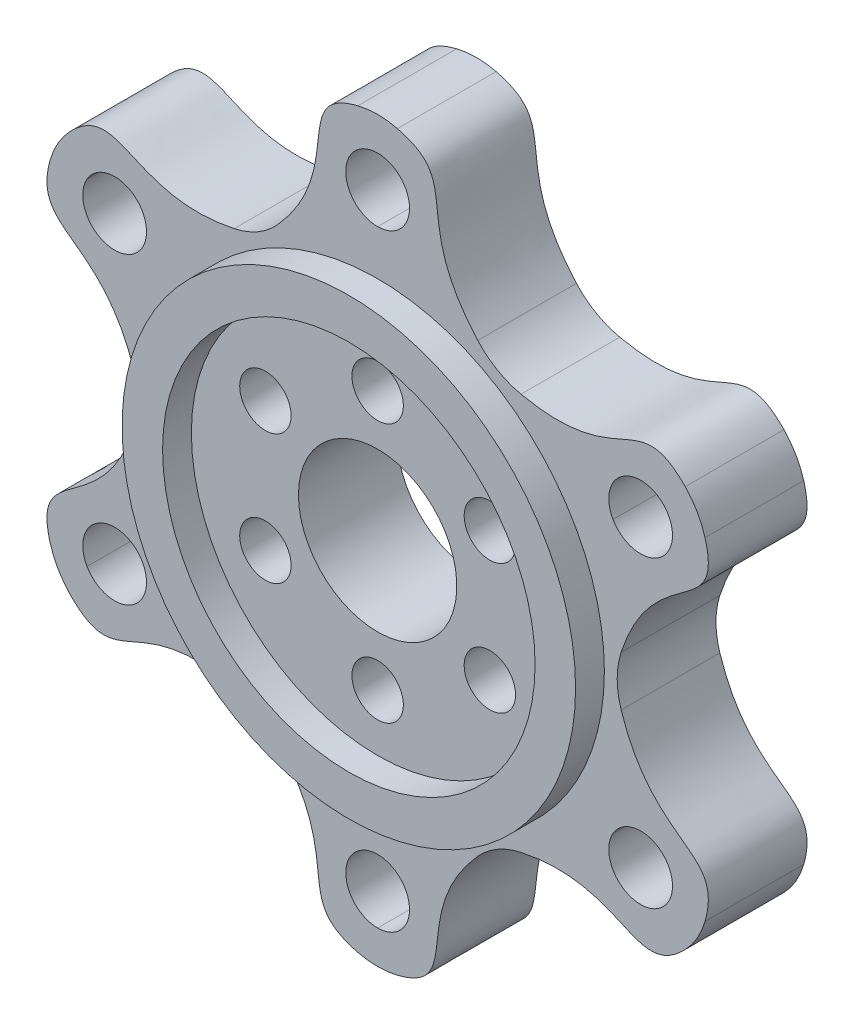
SolidWorks part; units mm, degrees
ref_plane "Front Plane" through (0, 0, 0) normal (0, 0, 1) x (1, 0, 0)
ref_plane "Top Plane" through (0, 0, 0) normal (0, 1, 0) x (1, 0, 0)
ref_plane "Right Plane" through (0, 0, 0) normal (1, 0, 0) x (0, 0, -1)
sketch "Sketch1" plane through (0, 0, 0) normal (0, 0, 1) x (1, 0, 0)
  line L0 (0, -55) -> (0, 55) construction
  line L1 (0, 0) -> (0, 45.72) construction
  circle A0 centre (0, 0) radius 9.779
  circle A1 centre (0, 0) radius 45.72
  circle A2 centre (0, 16.002) radius 3.175
  circle A3 centre (13.8581, 8.001) radius 3.175
  circle A4 centre (13.8581, -8.001) radius 3.175
  circle A5 centre (0, -16.002) radius 3.175
  circle A6 centre (-13.8581, -8.001) radius 3.175
  circle A7 centre (-13.8581, 8.001) radius 3.175
  circle A8 centre (0, 37.5) radius 3.937
  circle A10 centre (32.476, 18.75) radius 3.937
  circle A11 centre (32.476, -18.75) radius 3.937
  circle A12 centre (0, -37.5) radius 3.937
  circle A13 centre (-32.476, -18.75) radius 3.937
  circle A14 centre (-32.476, 18.75) radius 3.937
  point P21 (0, 0)
  point P36 (0, 0)
  dimension "D1" = 19.558
  dimension "D2" = 91.44
  dimension "D3" = 6.35
  dimension "D6" = 7.874
  dimension "D4" = 16.002
  dimension "D8" = 37.5
  dimension "D5" = 6
  dimension "D7" = 6
extrude "Boss-Extrude3" add sketch "Sketch1" along normal blind 12.192
sketch "Sketch2" plane through (0, 0, 12.192) normal (0, 0, 1) x (1, 0, 0)
  line L0 (0, -55) -> (0, 55) construction
  line L1 (-32.476, 18.75) -> (0, 37.5) construction
  line L2 (-16.238, 28.125) -> (-4.8895, 8.4689) construction
  line L3 (16.1981, 28.148) -> (4.8496, 8.4918) construction
  line L6 (32.476, -18.75) -> (32.476, 18.75) construction
  line L7 (32.476, 18.75) -> (0, 37.5) construction
  line L8 (55, 0) -> (-55, 0) construction
  circle A0 centre (0, 0) radius 27.94 construction
  circle A1 centre (0, 0) radius 45.72 construction
  circle A2 centre (0, 0) radius 9.779 construction
  circle A3 centre (0, 0) radius 45.72
  spline S0 degree 3 poles (-14.625, 25.3312) (-1.5745, 37.1177) (-13.1193, 43.9586) (0, 45.72) knots 0 0 0 0 1 1 1 1
  spline S1 degree 3 poles (14.625, 25.3312) (1.5745, 37.1177) (13.1193, 43.9586) (0, 45.72) knots 0 0 0 0 1 1 1 1
  spline S2 degree 3 poles (-29.25, 0) (-32.9321, 17.1953) (-44.6289, 10.6177) (-39.5947, 22.86) knots 0 0 0 0 1 1 1 1
  spline S3 degree 3 poles (-14.625, 25.3312) (-31.3576, 19.9224) (-31.5096, 33.3409) (-39.5947, 22.86) knots 0 0 0 0 1 1 1 1
  spline S4 degree 3 poles (-14.625, -25.3312) (-31.3576, -19.9224) (-31.5096, -33.3409) (-39.5947, -22.86) knots 0 0 0 0 1 1 1 1
  spline S5 degree 3 poles (-29.25, 0) (-32.9321, -17.1953) (-44.6289, -10.6177) (-39.5947, -22.86) knots 0 0 0 0 1 1 1 1
  spline S6 degree 3 poles (14.625, -25.3312) (31.3576, -19.9224) (31.5096, -33.3409) (39.5947, -22.86) knots 0 0 0 0 1 1 1 1
  spline S7 degree 3 poles (29.25, 0) (32.9321, -17.1953) (44.6289, -10.6177) (39.5947, -22.86) knots 0 0 0 0 1 1 1 1
  spline S8 degree 3 poles (14.625, -25.3312) (1.5745, -37.1177) (13.1193, -43.9586) (0, -45.72) knots 0 0 0 0 1 1 1 1
  spline S9 degree 3 poles (-14.625, -25.3312) (-1.5745, -37.1177) (-13.1193, -43.9586) (0, -45.72) knots 0 0 0 0 1 1 1 1
  spline S10 degree 3 poles (29.25, 0) (32.9321, 17.1953) (44.6289, 10.6177) (39.5947, 22.86) knots 0 0 0 0 1 1 1 1
  spline S11 degree 3 poles (14.625, 25.3312) (31.3576, 19.9224) (31.5096, 33.3409) (39.5947, 22.86) knots 0 0 0 0 1 1 1 1
  point P5 (-16.238, 28.125)
  point P6 (16.1981, 28.148)
  circle M8 centre (0, 0) radius 45.72
  dimension "D1" = 55.88
  dimension "D2" = 18.796
  dimension "D3" = 29.25
extrude "Cut-Extrude1" cut sketch "Sketch2" against normal blind 22.86 contours S1 S11 M8 | S5 S2 A3 | S10 S7 A3 | S6 S8 A3 | S9 S4 M8 | S3 S0 M8 region at (38.672, 0, 12.192) region at (19.336, 33.4909, 12.192) region at (19.336, -33.4909, 12.192) region at (-19.336, 33.4909, 12.192) region at (-19.336, -33.4909, 12.192) region at (-38.672, 0, 12.192)
sketch "Sketch4" plane through (0, 0, 12.192) normal (0, 0, 1) x (1, 0, 0)
  circle A0 centre (0, 0) radius 9.779 construction
  circle A1 centre (0, 0) radius 9.779 construction
  circle A2 centre (0, 0) radius 28
  circle A3 centre (0, 0) radius 23
  dimension "D1" = 56
  dimension "D2" = 46
extrude "Boss-Extrude4" add sketch "Sketch4" along normal blind 3.556 contours A2 | A3
ref_plane "Plane1" through (0, 0, 0) normal (1, 0, 0) x (0, 0, -1)
ref_plane "Plane2" through (0, 0, 0) normal (-0.5, -0.866, 0) x (-0.866, 0.5, 0)
ref_plane "Plane3" through (0, 0, 0) normal (-0.5, 0.866, 0) x (0.866, 0.5, 0)
split line "Split Line1"
split line "Split Line2"
split line "Split Line3"
ref_axis "Axis1" through (0, 0, 12.192) along (0, 0, -1)
fillet "Fillet1" radius 10 12 edges at (29.25, 0, 6.096) (39.5947, -22.86, 6.096) (0, -45.72, 6.096) (14.625, -25.3312, 6.096) (-14.625, -25.3312, 6.096) (-39.5947, -22.86, 6.096) (-29.25, 0, 6.096) (-39.5947, 22.86, 6.096) (-14.625, 25.3312, 6.096) (14.625, 25.3312, 6.096) (39.5947, 22.86, 6.096) (0, 45.72, 6.096)
